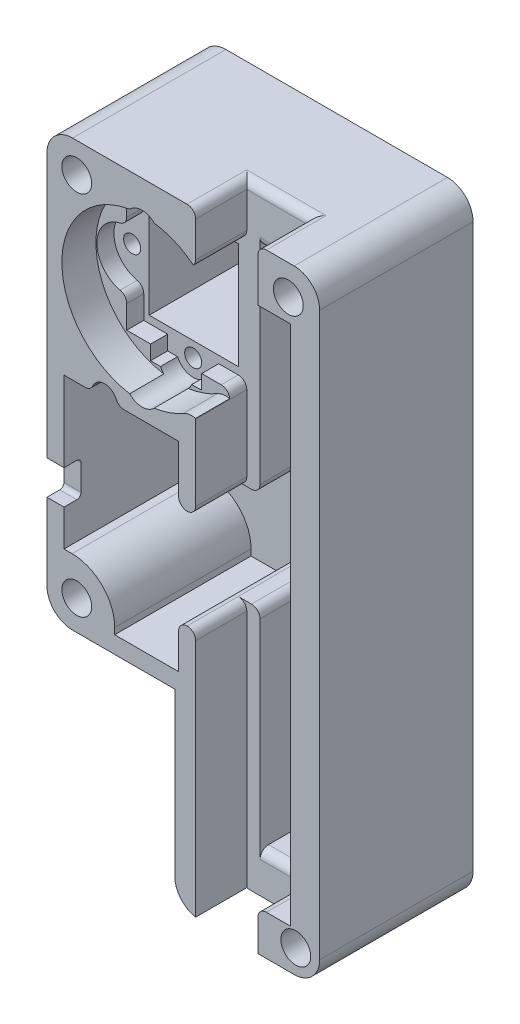
SolidWorks part; units mm, degrees
ref_plane "Ebene vorne" through (0, 0, 0) normal (0, 0, 1) x (1, 0, 0)
ref_plane "Ebene oben" through (0, 0, 0) normal (0, 1, 0) x (1, 0, 0)
ref_plane "Ebene rechts" through (0, 0, 0) normal (1, 0, 0) x (0, 0, -1)
sketch "body-sketch" plane through (0, 0, 0) normal (0, 0, 1) x (1, 0, 0)
  line L0 (-32, 50) -> (0, 50)
  line L1 (-32, 0) -> (-17, 0)
  line L2 (0, 50) -> (0, -22)
  line L3 (-17, -22) -> (-17, 0)
  line L4 (-32, 0) -> (-32, 50)
  line L5 (0, -22) -> (-17, -22)
  line L7 (-26, 43) -> (-15.5, 43)
  line L8 (-26, 43) -> (-26, 30.5)
  line L9 (-26, 30.5) -> (-15.5, 30.5)
  line L10 (-15.5, 43) -> (-15.5, 30.5)
  dimension "D1" = 32
  dimension "D2" = 50
  dimension "D3" = 17
  dimension "D4" = 72
  dimension "D5" = 12.5
  dimension "D6" = 10.5
  dimension "D7" = 7
  dimension "D8" = 6
extrude "body" add sketch "body-sketch" along normal mid plane 18
sketch "gear_box" plane through (0, 0, 9) normal (0, 0, 1) x (1, 0, 0)
  line L0 (-26, 43) -> (-15.5, 30.5) construction
  line L1 (-15.5, 30.5) -> (-15.5, 43) construction
  line L2 (-15.5, 43) -> (-26, 30.5) construction
  line L3 (0, 50) -> (-32, 50) construction
  line L4 (-32, 50) -> (-32, 0) construction
  circle A0 centre (-20.75, 36.75) radius 9.5
  dimension "D1" = 19
  dimension "D2" = 13.25
  dimension "D3" = 11.25
extrude "gear_profile" cut sketch "gear_box" against normal blind 4
sketch "screwhole1" plane through (0, 0, 9) normal (0, 0, 1) x (1, 0, 0)
  line L0 (0, 50) -> (-32, 50) construction
  line L1 (-32, 50) -> (-32, 0) construction
  line L2 (0, -22) -> (0, 50) construction
  line L3 (-17, -22) -> (0, -22) construction
  circle A0 centre (-28.5, 46.5) radius 1.75
  circle A1 centre (-3.6772, 46.5) radius 1.75
  circle A2 centre (-2.8, -19.2) radius 1.75
  dimension "D1" = 3.5
  dimension "D4" = 3.5
  dimension "D2" = 3.5
  dimension "D3" = 3.5
  dimension "D5" = 2.8
  dimension "D6" = 2.8
extrude "screw1" cut sketch "screwhole1" against normal through all
fillet "Verrundung2" radius 3 2 edges at (0, 50, 0) (-32, 50, 0)
sketch "glider" plane through (0, 0, 9) normal (0, 0, 1) x (1, 0, 0)
  line L0 (-17, 0) -> (-17, -22) construction
  line L1 (-13, 43.9) -> (-3.4, 43.9)
  line L2 (-13, 43.9) -> (-13, -17.3)
  line L3 (-13, -17.3) -> (-3.4, -17.3)
  line L4 (-3.4, 43.9) -> (-3.4, -17.3)
  line L5 (-3, 50) -> (-29, 50) construction
  dimension "D1" = 9.6
  dimension "D2" = 61.2
  dimension "D3" = 4
  dimension "D4" = 3.4
  dimension "D5" = 6.1
extrude "glider_rut" cut sketch "glider" against normal blind 16
fillet "Verrundung4" radius 2 1 edges at (-13, 31.2557, 7)
sketch "holder of glider" plane through (0, 0, -7) normal (0, 0, 1) x (1, 0, 0)
  line L5 (-11.2, 30.8) -> (-6.7, 30.8)
  line L6 (-11.2, 30.8) -> (-11.2, 22.8)
  line L7 (-11.2, 22.8) -> (-6.7, 22.8)
  line L8 (-6.7, 30.8) -> (-6.7, 22.8)
  line L9 (-9.7, 2.7) -> (-5.2, 2.7)
  line L10 (-9.7, 2.7) -> (-9.7, -5.3)
  line L11 (-9.7, -5.3) -> (-5.2, -5.3)
  line L12 (-5.2, 2.7) -> (-5.2, -5.3)
  line L13 (-9.7, 2.7) -> (-5.2, -5.3) construction
  line L14 (-9.7, -5.3) -> (-5.2, 2.7) construction
  line L15 (-11.2, 30.8) -> (-6.7, 22.8) construction
  line L16 (-11.2, 22.8) -> (-6.7, 30.8) construction
  point P6 (-8.95, 26.8)
  point P9 (-7.45, -1.3)
  dimension "D2" = 4.5
  dimension "D3" = 8
  dimension "D5" = 8
  dimension "D6" = 4.5
extrude "glider-holder" add sketch "holder of glider" along normal blind 4.3
fillet "Verrundung5" radius 2 8 edges at (-9.7, -5.3, -4.85) (-5.2, -5.3, -4.85) (-5.2, 2.7, -4.85) (-9.7, 2.7, -4.85) (-11.2, 30.8, -4.85) (-6.7, 30.8, -4.85) (-6.7, 22.8, -4.85) (-11.2, 22.8, -4.85)
fillet "Verrundung6" radius 1 8 edges at (-6.7, 26.8, -7) (-7.2858, 30.2142, -7) (-8.95, 30.8, -7) (-10.6142, 30.2142, -7) (-11.2, 26.8, -7) (-10.6142, 23.3858, -7) (-8.95, 22.8, -7) (-7.2858, 23.3858, -7)
fillet "Verrundung7" radius 1 8 edges at (-5.2, -1.3, -7) (-5.7858, 2.1142, -7) (-7.45, 2.7, -7) (-9.1142, 2.1142, -7) (-9.7, -1.3, -7) (-9.1142, -4.7142, -7) (-7.45, -5.3, -7) (-5.7858, -4.7142, -7)
sketch "Pinion rut" plane through (0, 0, 9) normal (0, 0, 1) x (1, 0, 0)
  line L0 (-9.5, 50) -> (-9.5, -22) construction
  line L1 (-3, 50) -> (-29, 50) construction
  line L2 (-17, -22) -> (0, -22) construction
  line L3 (0, -22) -> (0, 47) construction
  line L4 (-9.5, 14) -> (0, 14) construction
  line L6 (-11.75, 50) -> (-7.25, 50)
  line L7 (-11.75, 50) -> (-11.75, -22)
  line L8 (-11.75, -22) -> (-7.25, -22)
  line L9 (-7.25, 50) -> (-7.25, -22)
  line L10 (-11.75, 50) -> (-7.25, -22) construction
  line L11 (-11.75, -22) -> (-7.25, 50) construction
  dimension "D1" = 9.5
  dimension "D2" = 4.5
extrude "pinion rut cut" cut sketch "Pinion rut" against normal blind 5
fillet "Verrundung8" radius 2 1 edges at (-13, 42.2443, 7)
sketch "sketch pinion channel" plane through (0, 0, 9) normal (0, 0, 1) x (1, 0, 0)
  line L1 (-7.25, 50) -> (-14.55, 50)
  line L2 (-7.25, 50) -> (-7.25, -25)
  line L3 (-7.25, -25) -> (-14.55, -25)
  line L4 (-14.55, 50) -> (-14.55, -25)
  dimension "D1" = 7.3
  dimension "D2" = 75
extrude "pinion channel" cut sketch "sketch pinion channel" against normal blind 6
fillet "Verrundung10" radius 1 3 edges at (-7.25, -17.3, 6) (-7.25, 50, 6) (-14.55, 50, 6)
fillet "Verrundung11" radius 1 3 edges at (-10.125, 43.9, 3) (-9.625, -17.3, 3) (-10.9, 50, 3)
sketch "motor-holder" plane through (0, 0, 5) normal (0, 0, 1) x (1, 0, 0)
  line L0 (-14.3394, 43.85) -> (-14.3394, 29.65)
  line L1 (-15.5, 30.5) -> (-15.5, 43) construction
  line L2 (-15.5, 30.5) -> (-15.5, 43) construction
  line L3 (-15.5, 43) -> (-26, 43) construction
  line L4 (-17.8394, 27.95) -> (-17.8394, 29.65)
  line L7 (-20.75, 46.25) -> (-20.75, 27.25) construction
  line L8 (-26, 44.6675) -> (-26, 28.8325) construction
  line L9 (-26.6394, 43.85) -> (-23.8394, 43.85)
  line L10 (-23.8394, 45.55) -> (-17.8394, 45.55)
  line L11 (-23.8394, 43.85) -> (-23.8394, 45.55)
  line L12 (-23.8394, 27.95) -> (-17.8394, 27.95)
  line L13 (-17.8394, 29.65) -> (-14.3394, 29.65)
  line L14 (-17.8394, 45.55) -> (-17.8394, 43.85)
  line L15 (-17.8394, 43.85) -> (-14.3394, 43.85)
  line L17 (-26.6394, 43.85) -> (-26.6394, 29.65)
  line L23 (-23.8394, 27.95) -> (-23.8394, 29.65)
  line L24 (-23.8394, 29.65) -> (-26.6394, 29.65)
  arc A0 (-14.881, 44.2203) -> (-16, 28.5228) centre (-20.75, 36.75) ccw construction
  arc A1 (-14.881, 44.2203) -> (-16, 28.5228) centre (-20.75, 36.75) ccw construction
  point P25 (-20.75, 36.75)
  point P30 (-20.75, 36.75)
  dimension "D1" = 17.6
  dimension "D2" = 6
  dimension "D3" = 14.2
  dimension "D4" = 3.5
  dimension "D5" = 2.8
extrude "motor -holder" cut sketch "motor-holder" against normal blind 2
sketch "Skizze1" plane through (0, 0, 3) normal (0, 0, 1) x (1, 0, 0)
  line L0 (-20.8394, 45.55) -> (-20.8394, 27.95) construction
  line L1 (-17.8394, 45.55) -> (-23.8394, 45.55) construction
  line L2 (-23.8394, 27.95) -> (-17.8394, 27.95) construction
  line L3 (-26, 36.75) -> (-15.5, 36.75) construction
  line L4 (-26, 30.5) -> (-26, 43) construction
  line L5 (-15.5, 43) -> (-15.5, 30.5) construction
  circle A0 centre (-20.8394, 28.75) radius 1
  circle A1 centre (-20.8394, 44.75) radius 1
  point P16 (-20.8394, 36.75)
  dimension "D1" = 2
  dimension "D2" = 16
  dimension "D3" = 8
extrude "motor-screw" cut sketch "Skizze1" against normal blind 10
sketch "Skizze2" plane through (0, 0, 5) normal (0, 0, 1) x (1, 0, 0)
  circle A0 centre (-20.8394, 44.75) radius 2
  circle A1 centre (-20.8394, 28.75) radius 2
  dimension "D1" = 4
extrude "Schnitt-Linear austragen2" cut sketch "Skizze2" against normal blind 2 and the other way through all
sketch "Skizze3" plane through (0, 0, 5) normal (0, 0, 1) x (1, 0, 0)
  line L0 (-30.25, 36.75) -> (-13, 36.75) construction
  line L1 (-13, 44.9) -> (-13, -18.3) construction
  line L2 (-26.6394, 43.85) -> (-26.6394, 29.65) construction
  line L3 (-26.6394, 43.85) -> (-26.6394, 29.65) construction
  line L4 (-26.6394, 40.25) -> (-26.6394, 33.25)
  line L5 (-26.6394, 33.25) -> (-26.6589, 33.311)
  arc A0 (-22.2928, 46.1239) -> (-22.2928, 27.3761) centre (-20.75, 36.75) ccw construction
  arc A1 (-26.6394, 40.25) -> (-26.6394, 33.25) centre (-26.6394, 36.75) ccw
  point P8 (-26.6394, 36.75)
  dimension "D1" = 3.5
extrude "Schnitt-Linear austragen3" cut sketch "Skizze3" against normal blind 2
fillet "Verrundung12" radius 1 2 edges at (-14.55, 29.65, 4) (-14.55, 43.85, 4)
fillet "Verrundung13" radius 1 2 edges at (-26.6394, 33.25, 4) (-26.6394, 40.25, 4)
sketch "left hole" plane through (0, 0, 3) normal (0, 0, 1) x (1, 0, 0)
  line L0 (-30.1394, 36.75) -> (-15.5, 36.75) construction
  line L1 (-15.5, 43) -> (-15.5, 30.5) construction
  line L2 (-20.75, 43) -> (-20.75, 30.5) construction
  line L3 (-26, 43) -> (-15.5, 43) construction
  line L4 (-15.5, 30.5) -> (-26, 30.5) construction
  arc A0 (-27.4172, 40.1625) -> (-27.4172, 33.3375) centre (-26.6394, 36.75) ccw construction
  circle A1 centre (-28, 36.75) radius 1
  point P15 (-20.75, 36.75)
  dimension "D1" = 2
  dimension "D2" = 7.25
extrude "center-hole-left" cut sketch "left hole" against normal blind 10
sketch "cage" plane through (0, 0, 9) normal (0, 0, 1) x (1, 0, 0)
  line L2 (-30, 25.4121) -> (-30, 7.738)
  line L3 (-30, 25.4121) -> (-16.55, 25.4121)
  line L4 (-16.55, 25.4121) -> (-16.55, 18.8066)
  line L5 (-16.55, 18.8066) -> (-7.442, 18.8066)
  line L6 (-7.442, 18.8066) -> (-7.442, 7.14)
  line L7 (-14.55, 28.65) -> (-14.55, -22) construction
  line L8 (-14.55, 28.65) -> (-14.55, -22) construction
  line L9 (-7.442, 7.14) -> (-16.55, 7.14)
  line L10 (-16.55, 7.14) -> (-16.55, 2)
  line L11 (-30, 7.738) -> (-24.0525, 7.738)
  line L13 (-24.0525, 7.738) -> (-24.0525, 2)
  line L14 (-24.0525, 2) -> (-16.55, 2)
  point P7 (-24.0525, 13.9213)
  dimension "D2" = 2
  dimension "D3" = 2
extrude "electro-cage" cut sketch "cage" against normal blind 16
sketch "Skizze6" plane through (0, 0, 9) normal (0, 0, 1) x (1, 0, 0)
  line L0 (-16.55, 25.4121) -> (-30, 25.4121) construction
  circle A0 centre (-25.2373, 25.4121) radius 1.5
  dimension "D1" = 3
extrude "Schnitt-Linear austragen5" cut sketch "Skizze6" against normal blind 18
sketch "Skizze7" plane through (0, 0, 9) normal (0, 0, 1) x (1, 0, 0)
  line L0 (-32, 0) -> (-17, 0) construction
  line L1 (-32, 47) -> (-32, 0) construction
  circle A0 centre (-28.5, 3.5) radius 1.75
  dimension "D1" = 3.5
  dimension "D3" = 3.5
  dimension "D2" = 3.5
extrude "Schnitt-Linear austragen6" cut sketch "Skizze7" against normal blind 18
fillet "Verrundung14" radius 3 1 edges at (-32, 0, 0)
fillet "Verrundung15" radius 5 1 edges at (-24.0525, 7.738, 1)
fillet "Verrundung16" radius 1 1 edges at (-16.55, 18.8066, 1)
fillet "Verrundung17" radius 1 1 edges at (-16.55, 7.14, 1)
fillet "Verrundung18" radius 1 1 edges at (-23.7373, 25.4121, 1)
fillet "Verrundung19" radius 1 4 edges at (-13, 18.8066, -2) (-13, 7.14, -2) (-14.55, 7.14, 6) (-14.55, 18.8066, 6)
fillet "Verrundung20" radius 1 1 edges at (-26.7373, 25.4121, 1)
fillet "Verrundung21" radius 3 2 edges at (-17, -22, 0) (0, -22, 0)
sketch "Skizze8" plane through (0, 0, 9) normal (0, 0, 1) x (1, 0, 0)
  line L0 (-32, 47) -> (-32, 3) construction
  line L1 (-32, 16) -> (-30, 16)
  line L2 (-32, 16) -> (-32, 12)
  line L3 (-32, 12) -> (-30, 12)
  line L4 (-30, 16) -> (-30, 12)
  line L5 (-30, 25.4121) -> (-30, 7.738) construction
  line L6 (-29, 0) -> (-17, 0) construction
  point P8 (-23, 0)
  dimension "D1" = 4
  dimension "D2" = 12
extrude "Schnitt-Linear austragen7" cut sketch "Skizze8" against normal blind 2
fillet "Verrundung22" radius 0.5 2 edges at (-31, 12, 7) (-31, 16, 7)
